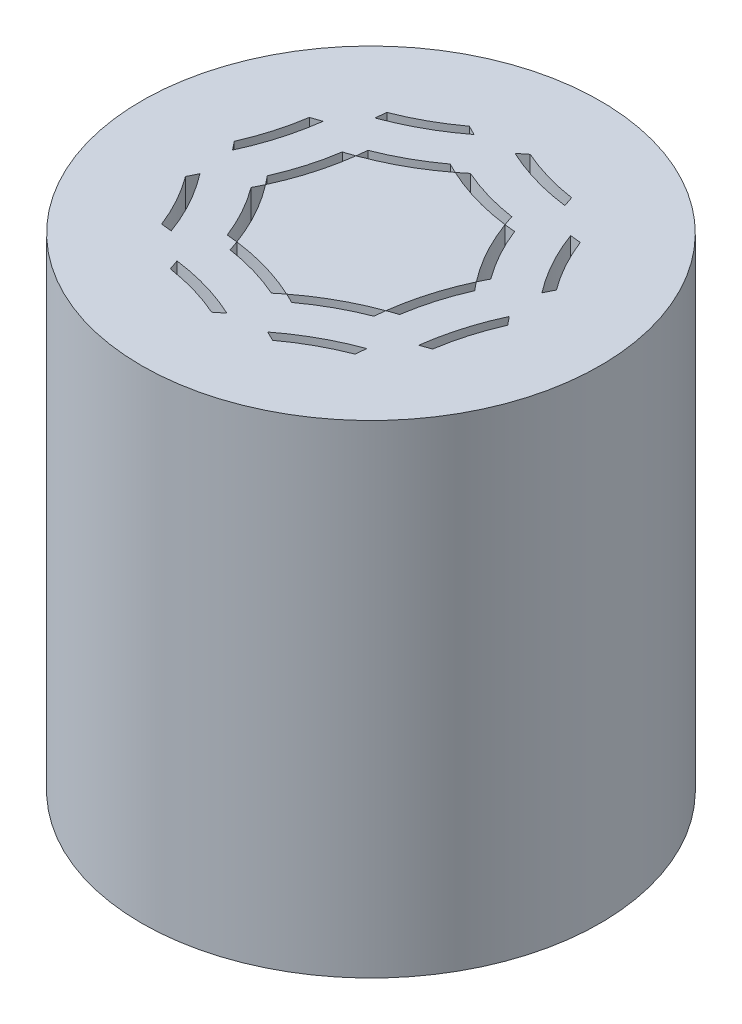
SolidWorks part; units mm, degrees
ref_plane "Front Plane" through (0, 0, 0) normal (0, 0, 1) x (1, 0, 0)
ref_plane "Top Plane" through (0, 0, 0) normal (0, 1, 0) x (1, 0, 0)
ref_plane "Right Plane" through (0, 0, 0) normal (1, 0, 0) x (0, 0, -1)
sketch "Sketch1" plane through (0, 0, 0) normal (0, 1, 0) x (1, 0, 0)
  circle A0 centre (0, 0) radius 4.75
  dimension "D1" = 9.5
extrude "Boss-Extrude1" add sketch "Sketch1" along normal blind 10
sketch "Sketch2" plane through (0, 10, 0) normal (0, 1, 0) x (1, 0, 0)
  circle A0 centre (0, 0) radius 4.75 construction
  arc A5 (-0.2449, 2.1983) -> (1.3813, 1.7276) centre (1.8677, 6.4526) ccw
  arc A6 (2.1983, 0.2449) -> (1.7276, -1.3813) centre (6.4526, -1.8677) ccw
  arc A7 (0.2449, -2.1983) -> (-1.3813, -1.7276) centre (-1.8677, -6.4526) ccw
  arc A8 (-2.1983, -0.2449) -> (-1.7276, 1.3813) centre (-6.4526, 1.8677) ccw
  arc A9 (-0.4196, 2.0628) -> (1.4566, 1.5197) centre (1.8677, 6.4526) ccw
  arc A10 (2.0628, 0.4196) -> (1.5197, -1.4566) centre (6.4526, -1.8677) ccw
  circle A11 centre (0, 0) radius 1.9675 construction
  arc A12 (0.4196, -2.0628) -> (-1.4566, -1.5197) centre (-1.8677, -6.4526) ccw
  arc A13 (-2.0628, -0.4196) -> (-1.5197, 1.4566) centre (-6.4526, 1.8677) ccw
  arc A14 (1.3813, 1.7276) -> (2.1983, 0.2449) centre (5.8834, 3.242) ccw
  arc A15 (1.7276, -1.3813) -> (0.2449, -2.1983) centre (3.242, -5.8834) ccw
  arc A16 (-1.3813, -1.7276) -> (-2.1983, -0.2449) centre (-5.8834, -3.242) ccw
  arc A17 (-1.7276, 1.3813) -> (-0.2449, 2.1983) centre (-3.242, 5.8834) ccw
  arc A18 (1.1619, 1.7554) -> (2.1046, 0.0446) centre (5.8834, 3.242) ccw
  arc A19 (-1.7554, 1.1619) -> (-0.0446, 2.1046) centre (-3.242, 5.8834) ccw
  arc A20 (-1.1619, -1.7554) -> (-2.1046, -0.0446) centre (-5.8834, -3.242) ccw
  arc A21 (1.7554, -1.1619) -> (0.0446, -2.1046) centre (3.242, -5.8834) ccw
  arc A23 (-2.2925, 4.1602) -> (4.1602, 2.2925) centre (1.8677, 6.4526) ccw construction
  arc A24 (-1.6203, 2.9403) -> (2.9403, 1.6203) centre (1.8677, 6.4526) ccw construction
  arc A25 (-2.9403, -1.6203) -> (-1.6203, 2.9403) centre (-6.4526, 1.8677) ccw construction
  arc A26 (-4.1602, -2.2925) -> (-2.2925, 4.1602) centre (-6.4526, 1.8677) ccw construction
  arc A27 (2.9403, 1.6203) -> (1.6203, -2.9403) centre (6.4526, -1.8677) ccw construction
  arc A28 (4.1602, 2.2925) -> (2.2925, -4.1602) centre (6.4526, -1.8677) ccw construction
  arc A29 (1.6203, -2.9403) -> (-2.9403, -1.6203) centre (-1.8677, -6.4526) ccw construction
  arc A30 (2.2925, -4.1602) -> (-4.1602, -2.2925) centre (-1.8677, -6.4526) ccw construction
  dimension "D1" = 9.5
  dimension "D2" = 0.2
  dimension "D3" = 2
sketch "Sketch3" plane through (0, 10, 0) normal (0, 1, 0) x (1, 0, 0)
  circle A0 centre (0, 0) radius 2
  dimension "D1" = 4
extrude "Cut-Extrude8" cut sketch "Sketch2" against normal blind 10 contours A13 A19 A9 A17 | A9 A19 A5 A17 | A19 A9 A18 A5 | A5 A18 A9 A14 | A9 A18 A10 A14 | A10 A18 A6 A14 | A21 A6 A18 A10 | A6 A21 A10 A15 | A10 A21 A12 A15 | A12 A21 A7 A15 | A21 A12 A20 A7 | A7 A20 A12 A16 | A12 A20 A13 A16 | A13 A20 A8 A16 | A20 A13 A19 A8 | A8 A19 A13 A17 region at (-0.2318, 10, -2.081) region at (0.523, 10, -1.8069) region at (-0.9078, 10, -1.6475) region at (1.3075, 10, -1.6354) region at (-1.6354, 10, -1.3075) region at (1.6475, 10, -0.9078) region at (-1.8069, 10, -0.523) region at (1.8069, 10, 0.523) region at (2.081, 10, -0.2318) region at (-1.6475, 10, 0.9078) region at (-2.081, 10, 0.2318) region at (1.6354, 10, 1.3075) region at (0.9078, 10, 1.6475) region at (-1.3075, 10, 1.6354) region at (-0.523, 10, 1.8069) region at (0.2318, 10, 2.081)
extrude "Boss-Extrude2" add sketch "Sketch2<9>" against normal up to surface (10 mm away) contours A9 A19 A5 A17 | A5 A18 A9 A14 | A10 A18 A6 A14 | A6 A21 A10 A15 | A12 A21 A7 A15 | A7 A20 A12 A16 | A13 A20 A8 A16 | A8 A19 A13 A17 region at (-0.2318, 10, -2.081) region at (1.3075, 10, -1.6354) region at (-1.6354, 10, -1.3075) region at (2.081, 10, -0.2318) region at (-2.081, 10, 0.2318) region at (1.6354, 10, 1.3075) region at (-1.3075, 10, 1.6354) region at (0.2318, 10, 2.081) up to face at (0, 0, 4.75)
sketch "Sketch2<9>" plane through (0, 10, 0) normal (0, 1, 0) x (1, 0, 0) same geometry as "Sketch2"
sketch "Sketch4" plane through (0, 10, 0) normal (0, 1, 0) x (1, 0, 0)
  line L0 (-1.5434, 1.234) -> (-1.5197, 1.4566)
  line L1 (-0.2188, 1.9639) -> (-0.4196, 2.0628)
  line L2 (0, 0) -> (-2.2925, 4.1602) construction
  line L3 (0, 0) -> (4.75, 0) construction
  line L4 (0, 0) -> (0, 4.75) construction
  line L5 (-0.7015, 2.8397) -> (-0.9023, 2.9386)
  line L6 (-2.0261, 2.1098) -> (-2.0024, 2.3324)
  arc A0 (-1.5434, 1.234) -> (-0.2188, 1.9639) centre (-3.242, 5.8834) ccw
  arc A1 (-1.5197, 1.4566) -> (-0.4196, 2.0628) centre (-3.242, 5.8834) ccw
  circle A2 centre (0, 0) radius 4.75 construction
  arc A3 (-2.0024, 2.3324) -> (-0.9023, 2.9386) centre (-3.7247, 6.7592) ccw
  arc A4 (-2.0261, 2.1098) -> (-0.7015, 2.8397) centre (-3.7247, 6.7592) ccw
  point P15 (-0.9496, 1.7232)
  dimension "D1" = 118.857
  dimension "D2" = 2
extrude "Cut-Extrude9" cut sketch "Sketch4" against normal blind 10 contours A3 L5 A4 L6
pattern_circular "CirPattern1" count 8 over 360 about axis through (0, 10, 0) along (0, -1, 0) of "Cut-Extrude9" reverse direction yes
sketch "Sketch5" plane through (0, 10, 0) normal (0, 1, 0) x (1, 0, 0)
  circle A2 centre (0, 0) radius 1.75
  dimension "D1" = 3.5
sketch "Sketch6" plane through (0, 0, 0) normal (0, -1, 0) x (1, 0, 0)
  circle A0 centre (0, 0) radius 1.75
  dimension "D1" = 3.5
scale "Scale3" bodies to scale 109 106 scale about centroid uniform scaling yes scale factor 5
sketch "Sketch7" plane through (0, -20, 0) normal (0, -1, 0) x (1, 0, 0)
  circle A0 centre (0, 0) radius 8.75
  dimension "D1" = 17.5
extrude "Boss-Extrude3" add sketch "Sketch7" along normal blind 5
